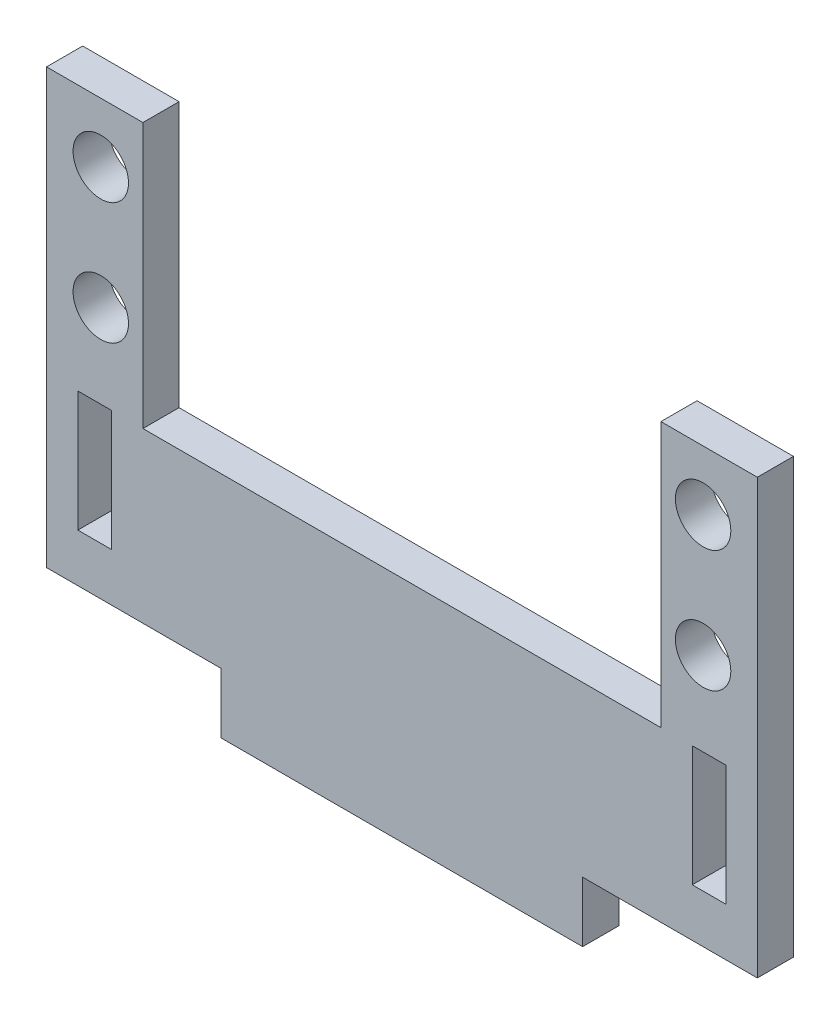
SolidWorks part; units mm, degrees
ref_plane "Front Plane" through (0, 0, 0) normal (0, 0, 1) x (1, 0, 0)
ref_plane "Top Plane" through (0, 0, 0) normal (0, 1, 0) x (1, 0, 0)
ref_plane "Right Plane" through (0, 0, 0) normal (1, 0, 0) x (0, 0, -1)
sketch "Sketch1" plane through (0, 0, 0) normal (0, 0, 1) x (1, 0, 0)
  line L1 (0, 0) -> (8, 0)
  line L2 (0, 0) -> (0, -36)
  line L3 (0, -36) -> (59, -36)
  line L4 (59, 0) -> (59, -36)
  line L8 (8, 0) -> (8, -22)
  line L9 (8, -22) -> (51, -22)
  line L10 (51, -22) -> (51, 0)
  line L14 (51, 0) -> (59, 0)
  circle A0 centre (4.5, -15.05) radius 2.3
  circle A1 centre (4.5, -4.95) radius 2.3
  circle A2 centre (54.5, -4.95) radius 2.3
  circle A3 centre (54.5, -15.05) radius 2.3
  dimension "D3" = 8
  dimension "D4" = 51
  dimension "D1" = 4.6
  dimension "D2" = 4.5
  dimension "D5" = 54.5
  dimension "D6" = 4.95
  dimension "D7" = 15.05
  dimension "D8" = 22
  dimension "D9" = 36
extrude "Boss-Extrude1" add sketch "Sketch1" along normal blind 3 contours L10 L9 L8 L1 L2 L3 L4 A3 A2 A1 A0 region at (29.5, -24.436, 0)
sketch "Sketch3" plane through (0, 0, 3) normal (0, 0, 1) x (1, 0, 0)
  line L1 (2.6, -22) -> (5.4, -22)
  line L2 (2.6, -22) -> (2.6, -32)
  line L3 (2.6, -32) -> (5.4, -32)
  line L4 (5.4, -22) -> (5.4, -32)
  line L5 (53.6, -22) -> (56.4, -22)
  line L6 (53.6, -22) -> (53.6, -32)
  line L7 (53.6, -32) -> (56.4, -32)
  line L8 (56.4, -22) -> (56.4, -32)
  line L10 (0, -36) -> (59, -36) construction
  line L11 (4, -22) -> (4, -32) construction
  line L12 (0, 0) -> (0, -36) construction
  line L13 (55, -22) -> (55, -32) construction
  line L14 (59, 0) -> (59, -36) construction
  dimension "D1" = 2.8
  dimension "D2" = 2.8
  dimension "D3" = 10
  dimension "D4" = 10
  dimension "D5" = 4
  dimension "D6" = 4
  dimension "D7" = 4
extrude "Cut-Extrude1" cut sketch "Sketch3" against normal blind 10
sketch "Sketch4" plane through (0, -36, 0) normal (0, -1, 0) x (1, 0, 0)
  line L0 (0, 3) -> (59, 3) construction
  line L1 (14.5, 3) -> (44.5, 3)
  line L2 (14.5, 3) -> (14.5, 0)
  line L3 (14.5, 0) -> (44.5, 0)
  line L4 (44.5, 3) -> (44.5, 0)
  line L5 (0, 0) -> (59, 0) construction
  line L6 (0, 3) -> (0, 0) construction
  dimension "D1" = 30
  dimension "D2" = 14.5
extrude "Boss-Extrude2" add sketch "Sketch4" along normal blind 5
